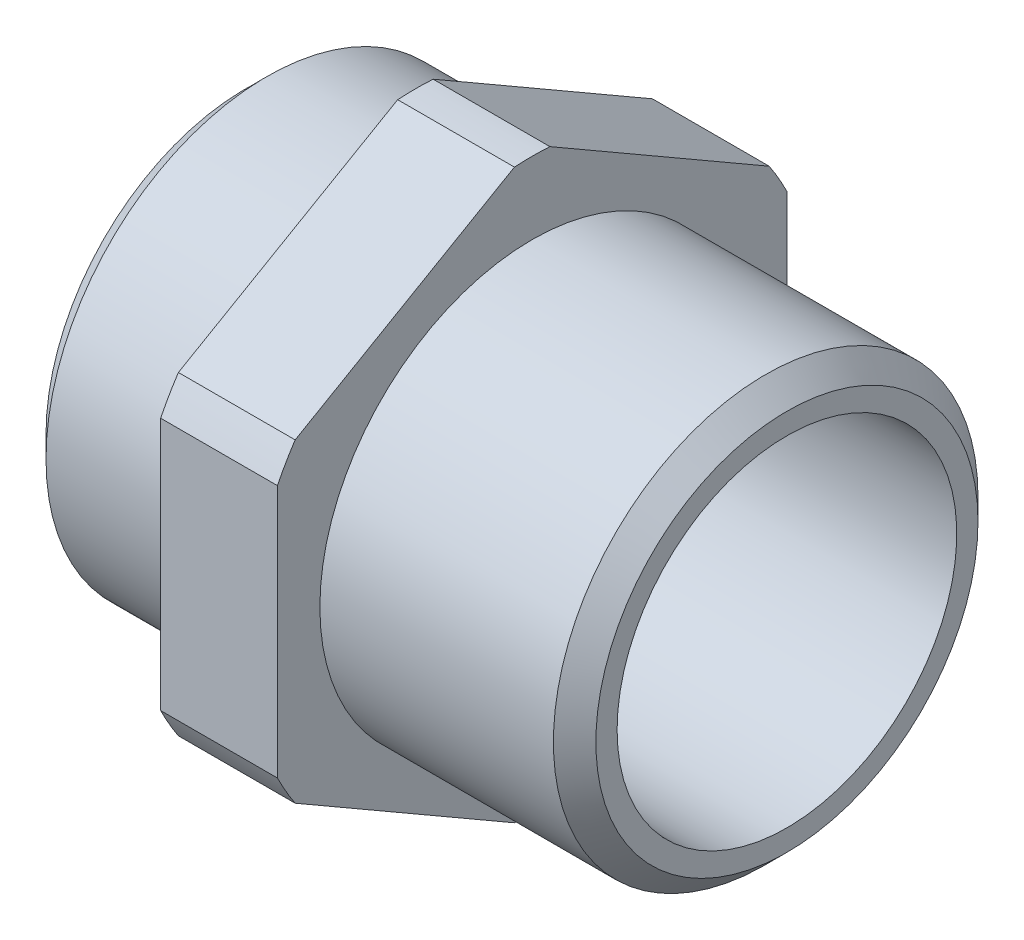
SolidWorks part; units mm, degrees
note: '?' marks a value the reader was unsure of.
ref_plane "Спереди" through (0, 0, 0) normal (0, 0, 1) x (1, 0, 0)
ref_plane "Сверху" through (0, 0, 0) normal (0, 1, 0) x (1, 0, 0)
ref_plane "Справа" through (0, 0, 0) normal (1, 0, 0) x (0, 0, -1)
sketch "Эскиз2" plane through (0, 0, 0) normal (1, 0, 0) x (0, 0, -1)
  circle A0 centre (0, 0) radius 10
  dimension "D1" = 20
extrude "Вытянуть1" add sketch "Эскиз2" against normal blind 12
sketch "Эскиз3" plane through (-12, 0, 0) normal (-1, 0, 0) x (0, 0, 1)
  line L0 (0, 13.8564) -> (-12, 6.9282)
  line L1 (-12, 6.9282) -> (-12, -6.9282)
  line L2 (-12, -6.9282) -> (0, -13.8564)
  line L3 (0, -13.8564) -> (12, -6.9282)
  line L4 (12, -6.9282) -> (12, 6.9282)
  line L5 (12, 6.9282) -> (0, 13.8564)
  circle A0 centre (0, 0) radius 13.8564
  circle M8 centre (0, 0) radius 10
  dimension "D1" = 120
  dimension "D2" = 24
extrude "Вытянуть2" add sketch "Эскиз3" along normal blind 5.5 contours L4 L5 L0 L1 L2 L3 M8 | M8
sketch "Эскиз4" plane through (-17.5, 0, 0) normal (-1, 0, 0) x (0, 0, 1)
  circle A0 centre (0, 0) radius 10.4
  dimension "D1" = 20.8
extrude "Вытянуть3" add sketch "Эскиз4" along normal blind 8
ref_axis "Ось1" through (1.6571, 0, 0) along (-1, 0, 0)?
sketch "Эскиз5" plane through (0, 0, 0) normal (0, 0, 1) x (1, 0, 0)
  line L0 (0, 0) -> (0, 8)
  line L2 (0, -10) -> (0, 10) construction
  line L3 (0, 8) -> (-16.7, 8)
  line L4 (-19, 8.5) -> (-17.5, 7)
  line L5 (-19, 8.5) -> (-25.5, 8.5)
  line L6 (-25.5, 10.4) -> (-25.5, -10.4) construction
  line L7 (-25.5, 8.5) -> (-25.5, 0)
  line L8 (-25.5, 0) -> (0, 0)
  line L9 (-25.5, 0) -> (-25.5, -8.5) construction
  line L10 (-25.5, -8.5) -> (-19, -8.5) construction
  line L11 (-17.5, 7) -> (-16.7, 7)
  line L12 (-16.7, -8) -> (0, -8) construction
  line L13 (0, -8) -> (0, 0) construction
  line L14 (-16.7, 7) -> (-16.7, 8)
  line L15 (-16.7, -8) -> (-16.7, -7) construction
  line L16 (-16.7, -7) -> (-17.5, -7) construction
  line L17 (-17.5, -7) -> (-19, -8.5) construction
  dimension "D1" = 17
  dimension "D2" = 14
  dimension "D3" = 16
  dimension "D4" = 16.7
  dimension "D5" = 6.5
  dimension "D6" = 45
revolve "Вырез-Повернуть1" cut sketch "Эскиз5" angle 360 about L8
sketch "Эскиз6" plane through (-17.5, 0, 0) normal (-1, 0, 0) x (0, 0, 1)
  circle A0 centre (0, 0) radius 13.8564
  circle A1 centre (0, 0) radius 13.4
  dimension "D1" = 26.8
extrude "Вырез-Вытянуть1" cut sketch "Эскиз6" against normal through all
chamfer "Фаска1" distance 1 angle 45 2 edges at (-25.5, 0, 10.4) (0, 0, -10)
sketch "Эскиз7" plane through (-16.7, 0, 0) normal (1, 0, 0) x (0, 0, -1)
  line L1 (-0.5, 0) -> (0.5, 0)
  line L2 (-0.5, 0) -> (-0.5, 8.5)
  line L3 (-0.5, 8.5) -> (0.5, 8.5)
  line L4 (0.5, 0) -> (0.5, 8.5)
  circle A0 centre (0, 0) radius 8.5 construction
  point P4 (0, 0)
  dimension "D1" = 1
extrude "Вытянуть4" add sketch "Эскиз7" against normal up to surface (8.8 mm away) up to face at (-25.5, 0, 9.4)
sketch "Эскиз8" plane through (-25.5, 0, 0) normal (-1, 0, 0) x (0, 0, 1)
  circle A0 centre (0, 0) radius 7
  arc A1 (-0.5, 6.9821) -> (0.5, 6.9821) centre (0, 0) ccw construction
extrude "Вырез-Вытянуть2" cut sketch "Эскиз8" against normal through all
sketch "Эскиз9" plane through (-25.5, 0, 0) normal (-1, 0, 0) x (0, 0, 1)
  circle A0 centre (0, 0) radius 8.5
  arc A1 (-0.5, 8.4853) -> (0.5, 8.4853) centre (0, 0) ccw construction
extrude "Вырез-Вытянуть3" cut sketch "Эскиз9" against normal blind 6.5
pattern_circular "Круговой массив1" count 6 over 360 about axis through (0, 0, 0) along (1, 0, 0) of "Вытянуть4", "Вырез-Вытянуть2", "Вырез-Вытянуть3"
